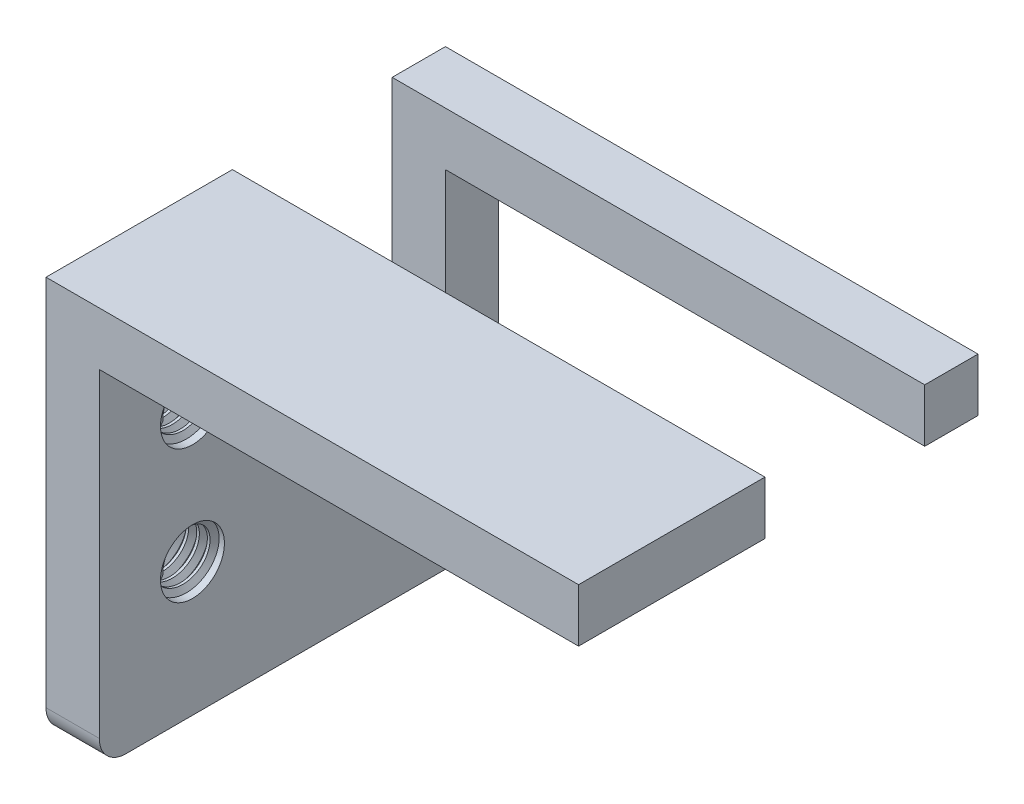
SolidWorks part; units mm, degrees
ref_plane "Front Plane" through (0, 0, 0) normal (0, 0, 1) x (1, 0, 0)
ref_plane "Top Plane" through (0, 0, 0) normal (0, 1, 0) x (1, 0, 0)
ref_plane "Right Plane" through (0, 0, 0) normal (1, 0, 0) x (0, 0, -1)
sketch "Sketch1" plane through (0, 0, 0) normal (0, 0, 1) x (1, 0, 0)
  line L0 (0, 0) -> (18, 0)
  line L1 (18, 0) -> (18, 2)
  line L2 (18, 2) -> (-2, 2)
  line L3 (-2, 2) -> (-2, -13)
  line L4 (-2, -13) -> (0, -13)
  line L5 (0, -13) -> (0, 0)
  dimension "D1" = 20
  dimension "D2" = 15
  dimension "D3" = 2
  dimension "D4" = 2
extrude "Boss-Extrude1" add sketch "Sketch1" along normal blind 15
sketch "Sketch2" plane through (0, 0, 0) normal (1, 0, 0) x (0, 0, -1)
  line L0 (-15, 2) -> (0, 2) construction
  line L1 (-8, 2) -> (-2, 2)
  line L2 (-8, 2) -> (-8, -5)
  line L3 (-8, -5) -> (-2, -5)
  line L4 (-2, 2) -> (-2, -5)
  line L5 (-15, -13) -> (-15, 0) construction
  line L6 (0, -13) -> (0, 0) construction
  dimension "D1" = 7
  dimension "D2" = 2
  dimension "D3" = 7
extrude "Cut-Extrude1" cut sketch "Sketch2" against normal through all both and the other way through all
hole_wizard "M2 Clearance Hole1" positions "Sketch4" profile "Sketch3" hole size "M2" standard "ISO" end condition through all
sketch "Sketch4" plane through (0, 0, 0) normal (1, 0, 0) x (0, 0, -1)
  line L0 (-15, -13) -> (-15, 0) construction
  line L1 (-15, 0) -> (-8, 0) construction
  point P0 (-11.5, -3)
  dimension "D1" = 3.5
  dimension "D2" = 3
sketch "Sketch3" plane through (0, -3, 11.5) normal (0, 1, 0) x (0, 0, -1)
  line L0 (0, 0) -> (0, 2)
  line L1 (0, 2) -> (1.2, 2)
  line L2 (1.2, 2) -> (1.2, 0)
  line L5 (1.2, 0) -> (0, 0)
  line L11 (0, -6.35) -> (0, 107.95) construction
  dimension "Thru Hole Dia." = 2.4
  dimension "Thru Hole Depth" = 2
thread "Thread1" pitch 0.4 method extrude profile "Thread Profile1" start angle 0, offset 0, length 0, pitch 0.4, diameter 2.4
ref_plane "Plane1" through (0, -3, 12.7) normal (0, -1, 0) x (0, 0, 1)
sketch "Thread Profile1" plane through (0, -3, 12.7) normal (0, -1, 0) x (0, 0, 1)
  line L0 (0, 0) -> (0, 0.4) construction
  line L11 (0, 0) -> (0, 0.35)
  line L12 (0, 0.35) -> (-0.2165, 0.225)
  line L13 (-0.2165, 0.225) -> (-0.2165, 0.125)
  line L15 (-0.2165, 0.125) -> (0, 0)
  line L17 (-0.2165, 0.175) -> (0, 0.175) construction
  point P2 (0, 0)
  dimension "Pitch" = 0.4
  dimension "Profile_Angle" = 60
  dimension "Profile_Land" = 0.1
  dimension "Profile_Height" = 0.2165
pattern_linear "LPattern2" count 2 spacing 5 along (0, -1, 0) of "Thread1", "M2 Clearance Hole1"
fillet "Fillet2" radius 1 2 edges at (-1, -13, 0) (-1, -13, 15)
